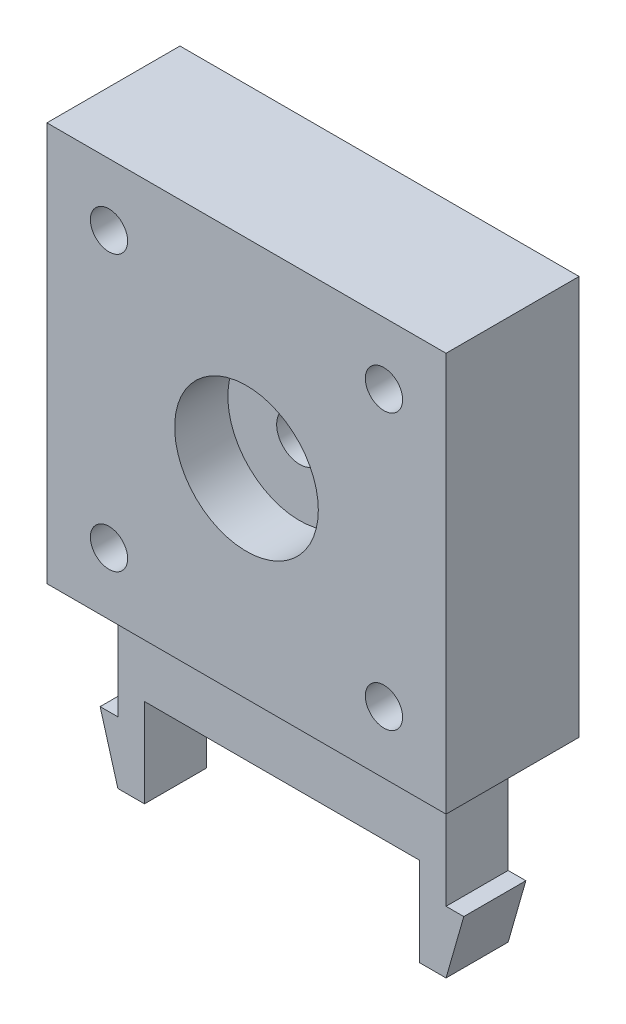
SolidWorks part; units mm, degrees
ref_plane "Front Plane" through (0, 0, 0) normal (0, 0, 1) x (1, 0, 0)
ref_plane "Top Plane" through (0, 0, 0) normal (0, 1, 0) x (1, 0, 0)
ref_plane "Right Plane" through (0, 0, 0) normal (1, 0, 0) x (0, 0, -1)
sketch "Sketch1" plane through (0, 0, 0) normal (0, 0, 1) x (1, 0, 0)
  line L1 (22.5, -22.5) -> (-22.5, -22.5)
  line L2 (22.5, -22.5) -> (22.5, 22.5)
  line L3 (22.5, 22.5) -> (-22.5, 22.5)
  line L4 (-22.5, -22.5) -> (-22.5, 22.5)
  line L5 (22.5, -22.5) -> (-22.5, 22.5) construction
  line L6 (22.5, 22.5) -> (-22.5, -22.5) construction
  circle A0 centre (0, 0) radius 2.6
  point P0 (0, 0)
  dimension "D3" = 5.2
  dimension "D1" = 45
  dimension "D2" = 45
extrude "Boss-Extrude1" add sketch "Sketch1" along normal mid plane 15
sketch "Sketch2" plane through (0, 0, 7.5) normal (0, 0, 1) x (1, 0, 0)
  circle A0 centre (0, 0) radius 8.1
  dimension "D1" = 16.2
extrude "Cut-Extrude1" cut sketch "Sketch2" against normal blind 6
sketch "Sketch5" plane through (0, 0, -7.5) normal (0, 0, -1) x (-1, 0, 0)
  circle A0 centre (0, 0) radius 8.1
  dimension "D1" = 16.2
extrude "Cut-Extrude4" cut sketch "Sketch5" against normal blind 6
sketch "Sketch6" plane through (0, 0, -7.5) normal (0, 0, 1) x (1, 0, 0)
  line L0 (19.2, 17.6362) -> (15.5, 19.7724)
  line L1 (15.5, -15.5) -> (-15.5, -15.5) construction
  line L2 (15.5, -15.5) -> (15.5, 15.5) construction
  line L3 (15.5, 15.5) -> (-15.5, 15.5) construction
  line L4 (-15.5, -15.5) -> (-15.5, 15.5) construction
  line L5 (15.5, -15.5) -> (-15.5, 15.5) construction
  line L6 (15.5, 15.5) -> (-15.5, -15.5) construction
  line L7 (-11.8, 17.6362) -> (-15.5, 19.7724)
  line L8 (-15.5, 19.7724) -> (-19.2, 17.6362)
  line L9 (-19.2, 17.6362) -> (-19.2, 13.3638)
  line L10 (-19.2, 13.3638) -> (-15.5, 11.2276)
  line L11 (-15.5, 11.2276) -> (-11.8, 13.3638)
  line L12 (-11.8, 13.3638) -> (-11.8, 17.6362)
  line L13 (15.5, 19.7724) -> (11.8, 17.6362)
  line L14 (11.8, 17.6362) -> (11.8, 13.3638)
  line L15 (11.8, 13.3638) -> (15.5, 11.2276)
  line L16 (15.5, 11.2276) -> (19.2, 13.3638)
  line L17 (19.2, 13.3638) -> (19.2, 17.6362)
  line L18 (19.2, -13.3638) -> (15.5, -11.2276)
  line L19 (15.5, -11.2276) -> (11.8, -13.3638)
  line L20 (11.8, -13.3638) -> (11.8, -17.6362)
  line L21 (11.8, -17.6362) -> (15.5, -19.7724)
  line L22 (15.5, -19.7724) -> (19.2, -17.6362)
  line L23 (19.2, -17.6362) -> (19.2, -13.3638)
  line L24 (-11.8, -13.3638) -> (-15.5, -11.2276)
  line L25 (-15.5, -11.2276) -> (-19.2, -13.3638)
  line L26 (-19.2, -13.3638) -> (-19.2, -17.6362)
  line L27 (-19.2, -17.6362) -> (-15.5, -19.7724)
  line L28 (-15.5, -19.7724) -> (-11.8, -17.6362)
  line L29 (-11.8, -17.6362) -> (-11.8, -13.3638)
  circle A4 centre (-15.5, 15.5) radius 3.7 construction
  circle A5 centre (15.5, 15.5) radius 3.7 construction
  circle A6 centre (15.5, -15.5) radius 3.7 construction
  circle A7 centre (-15.5, -15.5) radius 3.7 construction
  point P0 (0, 0)
  dimension "D2" = 2
  dimension "D1" = 31
  dimension "D3" = 7.4
  dimension "D4" = 2
sketch "Sketch7" plane through (0, -22.5, 0) normal (0, -1, 0) x (1, 0, 0)
  line L1 (18.5, -3.5) -> (-18.5, -3.5)
  line L2 (18.5, -3.5) -> (18.5, 3.5)
  line L3 (18.5, 3.5) -> (-18.5, 3.5)
  line L4 (-18.5, -3.5) -> (-18.5, 3.5)
  line L5 (18.5, -3.5) -> (-18.5, 3.5) construction
  line L6 (18.5, 3.5) -> (-18.5, -3.5) construction
  point P0 (0, 0)
  dimension "D1" = 37
  dimension "D2" = 7
extrude "Boss-Extrude2" add sketch "Sketch7" along normal blind 10
extrude "Cut-Extrude6" cut sketch "Sketch6" along normal blind 3.6 from offset 2
sketch "Sketch8" plane through (0, 0, -7.5) normal (0, 0, -1) x (-1, 0, 0)
  line L1 (15.5, -15.5) -> (-15.5, -15.5) construction
  line L2 (15.5, -15.5) -> (15.5, 15.5) construction
  line L3 (15.5, 15.5) -> (-15.5, 15.5) construction
  line L4 (-15.5, -15.5) -> (-15.5, 15.5) construction
  line L5 (15.5, -15.5) -> (-15.5, 15.5) construction
  line L6 (15.5, 15.5) -> (-15.5, -15.5) construction
  circle A0 centre (-15.5, 15.5) radius 2.1
  circle A1 centre (15.5, 15.5) radius 2.1
  circle A2 centre (15.5, -15.5) radius 2.1
  circle A3 centre (-15.5, -15.5) radius 2.1
  point P0 (0, 0)
  dimension "D2" = 4.2
  dimension "D1" = 31
  dimension "D3" = 2
  dimension "D4" = 2
extrude "Cut-Extrude7" cut sketch "Sketch8" against normal through all
sketch "Sketch9" plane through (0, -32.5, 0) normal (0, -1, 0) x (1, 0, 0)
  line L0 (-18.5, -3.5) -> (18.5, -3.5) construction
  line L1 (-18.5, 3.5) -> (-15.5, 3.5)
  line L2 (-18.5, 3.5) -> (-18.5, -3.5)
  line L3 (-18.5, -3.5) -> (-15.5, -3.5)
  line L4 (-15.5, 3.5) -> (-15.5, -3.5)
  line L5 (0, 3.5) -> (0, -3.5) construction
  line L6 (18.5, 3.5) -> (-18.5, 3.5) construction
  line L7 (-18.5, -3.5) -> (18.5, -3.5) construction
  line L8 (15.5, 3.5) -> (15.5, -3.5)
  line L9 (18.5, -3.5) -> (15.5, -3.5)
  line L10 (18.5, 3.5) -> (18.5, -3.5)
  line L11 (18.5, 3.5) -> (15.5, 3.5)
  dimension "D1" = 3
extrude "Boss-Extrude3" add sketch "Sketch9" along normal blind 10
sketch "Sketch10" plane through (-18.5, 0, 0) normal (-1, 0, 0) x (0, 0, 1)
  line L0 (3.5, -42.5) -> (3.5, -22.5) construction
  line L1 (-3.5, -42.5) -> (3.5, -42.5)
  line L2 (-3.5, -42.5) -> (-3.5, -35.5)
  line L3 (-3.5, -35.5) -> (3.5, -35.5)
  line L4 (3.5, -42.5) -> (3.5, -35.5)
  dimension "D1" = 7
extrude "Boss-Extrude4" add sketch "Sketch10" along normal blind 2
mirror "Mirror1" about plane through (0, 0, 0) normal (1, 0, 0) of "Boss-Extrude4"
chamfer "Chamfer2" distance 2 distance2 7 1 edges at (-20.5, -42.5, 0) first distance on face at (-18, -42.5, 0)
chamfer "Chamfer3" distance 7 distance2 2 1 edges at (20.5, -42.5, 0) first distance on face at (20.5, -39, 0)
